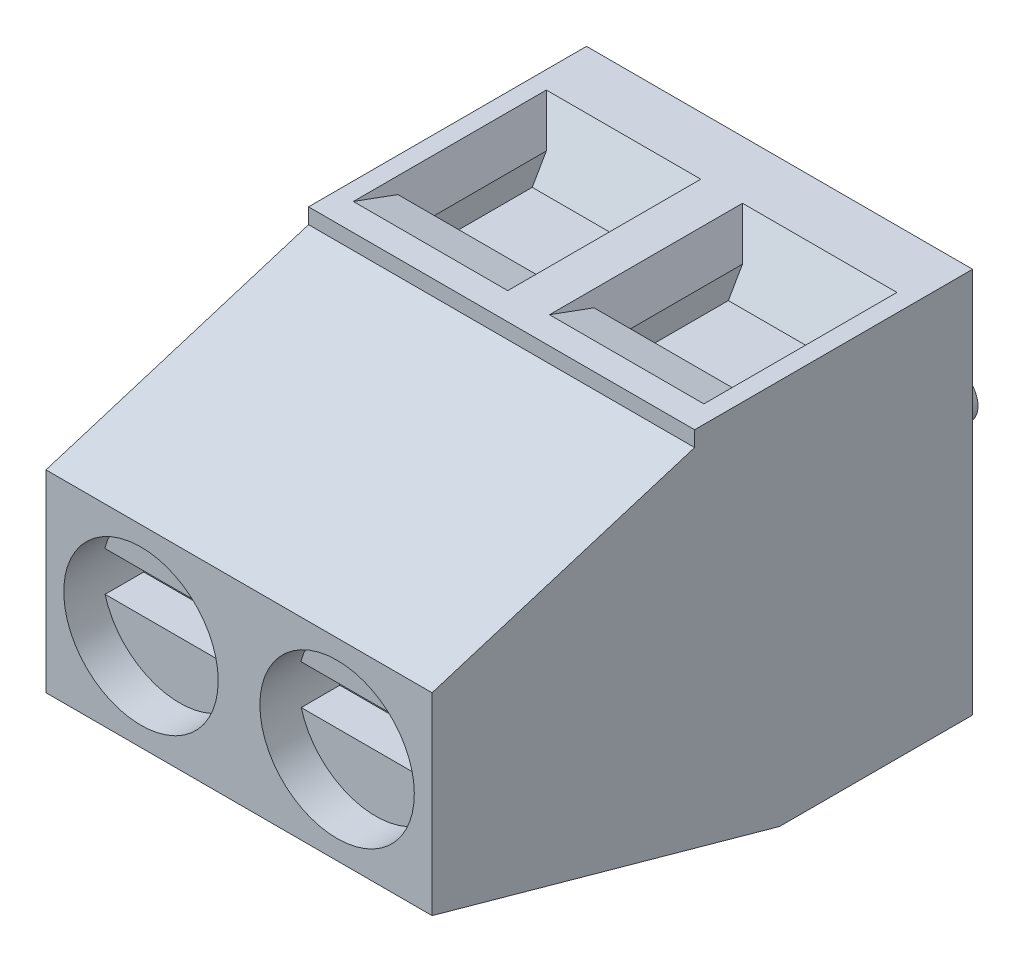
SolidWorks part; units mm, degrees
ref_plane "前视基准面" through (0, 0, 0) normal (0, 0, 1) x (1, 0, 0)
ref_plane "上视基准面" through (0, 0, 0) normal (0, 1, 0) x (1, 0, 0)
ref_plane "右视基准面" through (0, 0, 0) normal (1, 0, 0) x (0, 0, -1)
sketch "草图1" plane through (0, 0, 0) normal (0, 0, 1) x (1, 0, 0)
  line L0 (0, 0) -> (10, 0)
  line L1 (10, 0) -> (10, 10)
  line L2 (10, 10) -> (0, 10)
  line L3 (0, 10) -> (0, 0)
  dimension "D1" = 10
  dimension "D2" = 10
extrude "凸台-拉伸1" add sketch "草图1" along normal blind 14
sketch "草图2" plane through (10, 0, 0) normal (1, 0, 0) x (0, 0, -1)
  line L0 (-5, -2.1587) -> (-5, 11.6074) construction
  line L1 (-14, 5) -> (0, 5) construction
  line L2 (-14, 0) -> (-14, 10) construction
  line L3 (0, 0) -> (0, 10) construction
  line L4 (-14.7463, 2.5) -> (-12.0211, 2.5) construction
  line L5 (-14.7463, 7.5) -> (-12.0211, 7.5) construction
  line L6 (-14, 2.5) -> (-14, 0)
  line L7 (-14, 0) -> (-5, 0)
  line L8 (-14, 0) -> (0, 0) construction
  line L9 (-5, 0) -> (-14, 2.5)
  line L10 (-7.2, 8.4224) -> (-7.2, 10.8731) construction
  line L11 (-14, 7.5) -> (-14, 10)
  line L12 (-14, 10) -> (-7.2, 10)
  line L13 (-14, 10) -> (0, 10) construction
  line L14 (-7.2, 10) -> (-7.2, 9.6)
  line L15 (-7.2, 9.6) -> (-14, 7.5)
  dimension "D1" = 5
  dimension "D2" = 2.5
  dimension "D3" = 7.2
  dimension "D4" = 0.4
extrude "切除-拉伸1" cut sketch "草图2" against normal through all
sketch "草图3" plane through (0, 10, 0) normal (0, 1, 0) x (1, 0, 0)
  line L0 (5, -14) -> (5, 0) construction
  line L1 (0, -14) -> (10, -14) construction
  line L2 (10, 0) -> (0, 0) construction
  line L3 (2.46, -7.9133) -> (2.46, 0.618) construction
  line L4 (0.96, -5.5) -> (0.96, -2.5)
  line L5 (3.96, -5.5) -> (3.96, -2.5)
  line L6 (3.96, -5.5) -> (0.96, -5.5)
  line L7 (3.96, -2.5) -> (0.96, -2.5)
  line L8 (6.04, -2.5) -> (9.04, -2.5)
  line L9 (9.04, -5.5) -> (9.04, -2.5)
  line L10 (6.04, -5.5) -> (9.04, -5.5)
  line L11 (6.04, -5.5) -> (6.04, -2.5)
  dimension "D1" = 2.54
  dimension "D2" = 2.5
  dimension "D3" = 3
  dimension "D4" = 3
extrude "切除-拉伸2" cut sketch "草图3" against normal blind 1.5
chamfer "倒角1" distance 1 angle 15 2 edges at (2.46, 10, 5.5) (7.54, 10, 5.5) first distance on face at (7.54, 10, 4)
chamfer "倒角2" distance 1 angle 60 2 edges at (2.46, 10, 2.5) (7.54, 10, 2.5) first distance on face at (7.54, 10, 4.5)
chamfer "倒角3" distance 0.5 angle 60 4 edges at (0.96, 10, 4) (3.96, 10, 4) (6.04, 10, 4) (9.04, 10, 4) first distance on face at (7.54, 10, 4)
sketch "草图4" plane through (0, 0, 0) normal (0, -1, 0) x (1, 0, 0)
  line L0 (-2.5668, 2.5) -> (13.7578, 2.5) construction
  line L1 (5, 0) -> (5, 7.4883) construction
  line L2 (0, 0) -> (10, 0) construction
  line L3 (7.54, 6.1609) -> (7.54, -1.1027) construction
  line L4 (8.54, 2.5) -> (8.54, 7)
  line L5 (6.54, 2.5) -> (6.54, 7)
  line L6 (6.54, 2.5) -> (8.54, 2.5)
  line L7 (6.54, 7) -> (8.54, 7)
  line L8 (3.46, 2.5) -> (1.46, 2.5)
  line L9 (3.46, 7) -> (1.46, 7)
  line L10 (1.46, 2.5) -> (1.46, 7)
  line L11 (3.46, 2.5) -> (3.46, 7)
  dimension "D1" = 2.5
  dimension "D2" = 2.54
  dimension "D3" = 4.5
  dimension "D4" = 2
extrude "切除-拉伸3" cut sketch "草图4" against normal blind 1.5
sketch "草图5" plane through (0, 0, 14) normal (0, 0, 1) x (1, 0, 0)
  line L0 (0, 5) -> (10, 5) construction
  line L1 (0, 7.5) -> (0, 2.5) construction
  line L2 (10, 2.5) -> (10, 7.5) construction
  line L3 (5, 7.5) -> (5, 2.5) construction
  line L4 (0, 7.5) -> (10, 7.5) construction
  line L5 (0, 2.5) -> (10, 2.5) construction
  circle A0 centre (2.46, 5) radius 2
  circle A1 centre (7.54, 5) radius 2
  dimension "D1" = 4
  dimension "D2" = 5.08
extrude "切除-拉伸4" cut sketch "草图5" against normal blind 1
sketch "草图6" plane through (0, 0, 13) normal (0, 0, 1) x (1, 0, 0)
  line L0 (0.5235, 5.5) -> (4.3965, 5.5)
  line L1 (2.46, 5) -> (-1.8707, 5) construction
  line L2 (0.5305, 4.4737) -> (4.3895, 4.4737)
  line L3 (5, 7.5) -> (5, 2.5) construction
  line L4 (0, 7.5) -> (10, 7.5) construction
  line L5 (0, 2.5) -> (10, 2.5) construction
  line L6 (9.4695, 4.4737) -> (5.6105, 4.4737)
  line L7 (9.4765, 5.5) -> (5.6035, 5.5)
  arc A0 (0.5235, 5.5) -> (0.5305, 4.4737) centre (2.46, 5) ccw
  arc A1 (4.3895, 4.4737) -> (4.3965, 5.5) centre (2.46, 5) ccw
  arc A2 (5.6105, 4.4737) -> (5.6035, 5.5) centre (7.54, 5) cw
  arc A3 (9.4765, 5.5) -> (9.4695, 4.4737) centre (7.54, 5) cw
  dimension "D1" = 4
  dimension "D2" = 1
extrude "切除-拉伸5" cut sketch "草图6" against normal blind 1
sketch "草图7" plane through (0, 0, 0) normal (0, 0, -1) x (-1, 0, 0)
  line L0 (-5, 0) -> (-5, 10) construction
  line L1 (0, 0) -> (-10, 0) construction
  line L2 (-10, 10) -> (0, 10) construction
  line L3 (-10, 5) -> (0, 5) construction
  line L4 (-10, 0) -> (-10, 10) construction
  line L5 (0, 10) -> (0, 0) construction
  circle A0 centre (-7.54, 5) radius 0.6
  circle A1 centre (-2.46, 5) radius 0.6
  dimension "D1" = 1.2
  dimension "D2" = 5.08
extrude "凸台-拉伸2" add sketch "草图7" along normal blind 2
